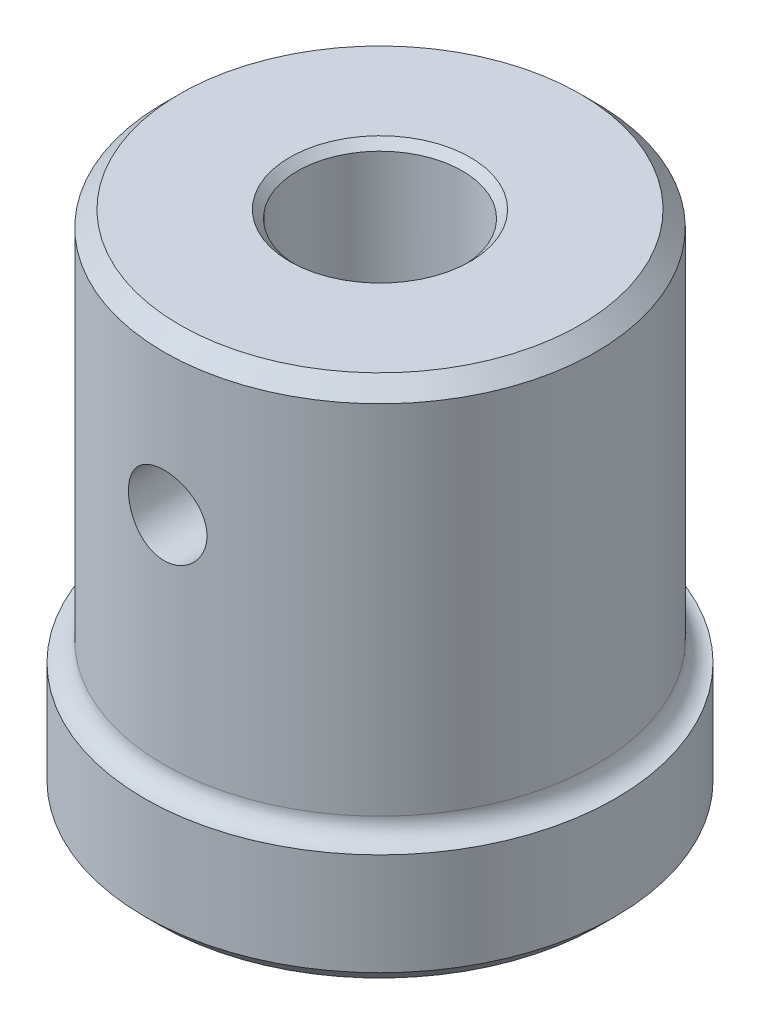
SolidWorks part; units mm, degrees
material "1.0060 (E335)"
ref_plane "Front Plane" through (0, 0, 0) normal (0, 0, 1) x (1, 0, 0)
ref_plane "Top Plane" through (0, 0, 0) normal (0, 1, 0) x (1, 0, 0)
ref_plane "Right Plane" through (0, 0, 0) normal (1, 0, 0) x (0, 0, -1)
sketch "Sketch1" plane through (0, 0, 0) normal (0, 1, 0) x (1, 0, 0)
  circle A0 centre (0, 0) radius 30
  dimension "D1" = 60
extrude "Boss-Extrude1" add sketch "Sketch1" along normal blind 15
sketch "Sketch2" plane through (0, 15, 0) normal (0, 1, 0) x (1, 0, 0)
  circle A0 centre (0, 0) radius 27.5
  dimension "D1" = 55
extrude "Boss-Extrude2" add sketch "Sketch2" along normal blind 50
sketch "Sketch3" plane through (0, 65, 0) normal (0, 1, 0) x (1, 0, 0)
  circle A0 centre (0, 0) radius 10.5
  dimension "D1" = 21
extrude "Cut-Extrude1" cut sketch "Sketch3" against normal blind 50
chamfer "Chamfer1" distance 2 angle 45 2 edges at (0, 65, 27.5) (0, 0, 30)
chamfer "Chamfer2" distance 1 angle 45 1 edges at (0, 65, 10.5)
fillet "Fillet1" radius 2.5 1 edges at (0, 15, 27.5)
sketch "Sketch4" plane through (0, 0, 0) normal (0, 0, 1) x (1, 0, 0)
  line L0 (0, -1000) -> (0, 49000) construction
  line L1 (0, 18) -> (-10.5, 18)
  line L2 (0, 15) -> (-10.5, 15)
  line L3 (0, 15) -> (0, 18)
  arc A0 (-10.5, 15) -> (-10.5, 18) centre (-10.5, 16.5) cw
  dimension "D1" = 3
  dimension "D2" = 21
  dimension "D3" = 15
revolve "Cut-Revolve1" cut sketch "Sketch4" angle 360 about L0
sketch "Sketch5" plane through (0, 0, 0) normal (0, 0, 1) x (1, 0, 0)
  line L0 (25.5, 65) -> (-25.5, 65) construction
  circle A0 centre (0, 45) radius 5
  dimension "D1" = 10
  dimension "D2" = 20
extrude "Cut-Extrude2" cut sketch "Sketch5" against normal through all both and the other way through all
